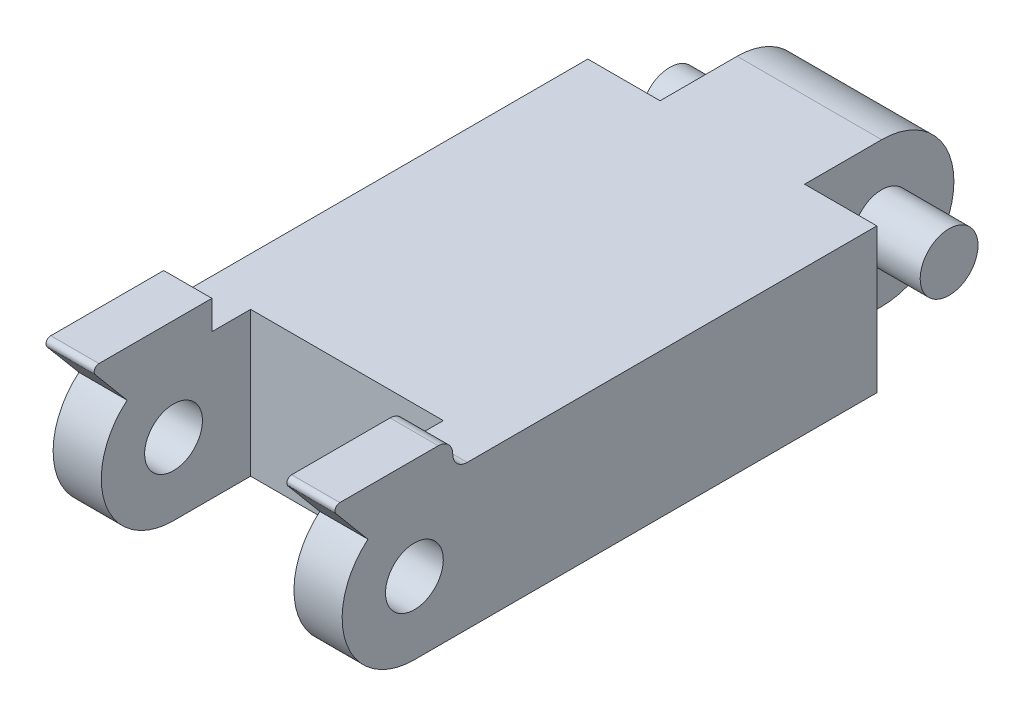
SolidWorks part; units mm, degrees
ref_plane "前视基准面" through (0, 0, 0) normal (0, 0, 1) x (1, 0, 0)
ref_plane "上视基准面" through (0, 0, 0) normal (0, 1, 0) x (1, 0, 0)
ref_plane "右视基准面" through (0, 0, 0) normal (1, 0, 0) x (0, 0, -1)
sketch "草图1" plane through (0, 0, 0) normal (0, 0, 1) x (1, 0, 0)
  line L1 (-15, 7.5) -> (15, 7.5)
  line L2 (-15, 7.5) -> (-15, -7.5)
  line L3 (-15, -7.5) -> (15, -7.5)
  line L4 (15, 7.5) -> (15, -7.5)
  line L5 (-15, 7.5) -> (15, -7.5) construction
  line L6 (-15, -7.5) -> (15, 7.5) construction
  point P0 (0, 0)
  dimension "D1" = 30
  dimension "D2" = 15
extrude "凸台-拉伸1" add sketch "草图1" along normal blind 40
sketch "草图2" plane through (15, 0, 0) normal (1, 0, 0) x (0, 0, -1)
  line L0 (-40, -7.5) -> (-48, -7.5)
  line L1 (-48, 7.5) -> (-40, 7.5)
  line L2 (-40, -7.5) -> (-40, 7.5)
  arc A0 (-48, -7.5) -> (-48, 7.5) centre (-48, 0) cw
  dimension "D1" = 8
extrude "凸台-拉伸2" add sketch "草图2" against normal blind 5
sketch "草图3" plane through (15, 0, 0) normal (1, 0, 0) x (0, 0, -1)
  circle A0 centre (-48, 0) radius 3
  dimension "D1" = 6
extrude "切除-拉伸1" cut sketch "草图3" against normal up to surface (5 mm away) up to face at (10, 0, 45.875)
mirror "镜向1" about plane through (0, 0, 0) normal (1, 0, 0) of "切除-拉伸1", "凸台-拉伸2"
sketch "草图6" plane through (0, 0, 0) normal (1, 0, 0) x (0, 0, -1)
  line L0 (0, 7.5) -> (8, 7.5)
  line L1 (8, -7.5) -> (0, -7.5)
  line L2 (0, 7.5) -> (0, -7.5)
  arc A0 (8, 7.5) -> (8, -7.5) centre (8, 0) cw
  dimension "D1" = 8
extrude "凸台-拉伸3" add sketch "草图6" along normal mid plane 15
sketch "草图7" plane through (7.5, 0, 0) normal (1, 0, 0) x (0, 0, -1)
  circle A0 centre (8, 0) radius 3
  dimension "D1" = 6
extrude "凸台-拉伸4" add sketch "草图7" along normal blind 7
mirror "镜向2" about plane through (0, 0, 0) normal (1, 0, 0) of "凸台-拉伸4"
sketch "草图8" plane through (15, 0, 0) normal (1, 0, 0) x (0, 0, -1)
  line L0 (-48, 0) -> (-56.8105, 10.5) construction
  line L1 (-52.8209, 5.7453) -> (-56.8105, 10.5)
  line L2 (-56.8105, 10.5) -> (-44.0197, 10.5)
  line L3 (-44.0197, 10.5) -> (-44.0197, 7.5)
  line L4 (-48, 7.5) -> (0, 7.5) construction
  line L5 (-44.0197, 7.5) -> (-48, 7.5)
  line L6 (-48, 0) -> (-48, 3) construction
  arc A0 (-48, 7.5) -> (-48, -7.5) centre (-48, 0) ccw construction
  arc A1 (-48, 7.5) -> (-48, -7.5) centre (-48, 0) ccw
  circle A2 centre (-48, 0) radius 3 construction
  line M6 (0, 7.5) -> (-48, 7.5)
  arc M7 (-48, 7.5) -> (-48, -7.5) centre (-48, 0) ccw
  dimension "D1" = 40
  dimension "D2" = 3
extrude "凸台-拉伸5" add sketch "草图8" against normal blind 5 contours L3 L2 L1 M7 M6 region at (15, 8.8395, 50.0534)
fillet "圆角2" radius 1.5 2 edges at (12.5, 7.5, 44.0197) (12.5, 10.5, 44.0197)
fillet "圆角3" radius 0.5 1 edges at (12.5, 10.5, 56.8105)
mirror "镜向3" about plane through (0, 0, 0) normal (1, 0, 0) of "凸台-拉伸5", "圆角3"
